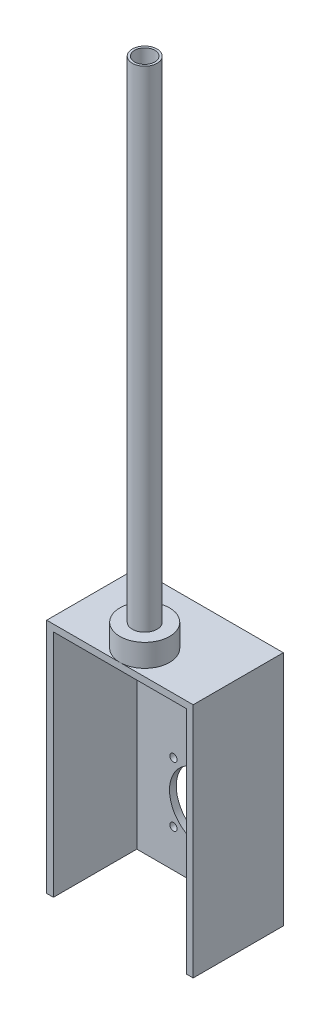
SolidWorks part; units mm, degrees
ref_plane "前视基准面" through (0, 0, 0) normal (0, 0, 1) x (1, 0, 0)
ref_plane "上视基准面" through (0, 0, 0) normal (0, 1, 0) x (1, 0, 0)
ref_plane "右视基准面" through (0, 0, 0) normal (1, 0, 0) x (0, 0, -1)
sketch "草图1" plane through (0, 0, 0) normal (0, 1, 0) x (1, 0, 0)
  circle A0 centre (0, 0) radius 22
  dimension "D1" = 44
extrude "凸台-拉伸1" add sketch "草图1" along normal blind 20
sketch "草图2" plane through (0, 20, 0) normal (0, 1, 0) x (1, 0, 0)
  circle A0 centre (0, 0) radius 11
  dimension "D1" = 22
extrude "凸台-拉伸2" add sketch "草图2" along normal blind 435
sketch "草图3" plane through (0, 455, 0) normal (0, 1, 0) x (1, 0, 0)
  circle A0 centre (0, 0) radius 8
  dimension "D1" = 16
sketch "草图4" plane through (0, 0, 0) normal (0, -1, 0) x (1, 0, 0)
  line L1 (-65, 22) -> (65, 22)
  line L2 (-65, 22) -> (-65, -58)
  line L3 (-65, -58) -> (65, -58)
  line L4 (65, 22) -> (65, -58)
  line L5 (-65, 22) -> (65, -58) construction
  line L6 (-65, -58) -> (65, 22) construction
  circle A1 centre (0, 0) radius 22 construction
  point P8 (0, -18)
  dimension "D1" = 130
  dimension "D2" = 80
extrude "凸台-拉伸3" add sketch "草图4" along normal blind 210 separate body
shell "抽壳2" thickness 6 removed face at (0, -105, 22)
extrude "切除-拉伸2" cut sketch "草图3" against normal up to surface (461 mm away) contours A0 up to face at (0, -6, -15)
sketch "草图5" plane through (0, 0, 22) normal (0, 0, 1) x (1, 0, 0)
  line L0 (65, -210) -> (-65, -210) construction
  line L1 (59, -204) -> (-59, -204)
  line L2 (59, -204) -> (59, -210)
  line L3 (59, -210) -> (-59, -210)
  line L4 (-59, -204) -> (-59, -210)
extrude "切除-拉伸3" cut sketch "草图5" against normal up to surface (74 mm away) up to face at (0, -105, -52)
sketch "草图6" plane through (0, 0, -58) normal (0, 0, -1) x (-1, 0, 0)
  line L1 (0, -150) -> (82.393, -67.607) construction
  line L2 (65, -210) -> (65, 0) construction
  circle A0 centre (0, -150) radius 30
  circle A1 centre (26.5165, -123.4835) radius 3.25
  circle A2 centre (26.5165, -176.5165) radius 3.25
  circle A3 centre (-26.5165, -176.5165) radius 3.25
  circle A4 centre (-26.5165, -123.4835) radius 3.25
  point P21 (0, -150)
  dimension "D1" = 60
  dimension "D5" = 6.5
  dimension "D2" = 150
  dimension "D3" = 135
  dimension "D4" = 37.5
  dimension "D6" = 4
extrude "切除-拉伸4" cut sketch "草图6" against normal blind 10
sketch "草图7" plane through (0, 455, 0) normal (0, 1, 0) x (1, 0, 0)
  circle A0 centre (0, 0) radius 9
  dimension "D1" = 18
extrude "切除-拉伸5" cut sketch "草图7" against normal blind 18
sketch "草图8" plane through (0, -6, 0) normal (0, -1, 0) x (1, 0, 0)
  circle A0 centre (0, 0) radius 9
  dimension "D1" = 18
extrude "切除-拉伸6" cut sketch "草图8" against normal blind 18
